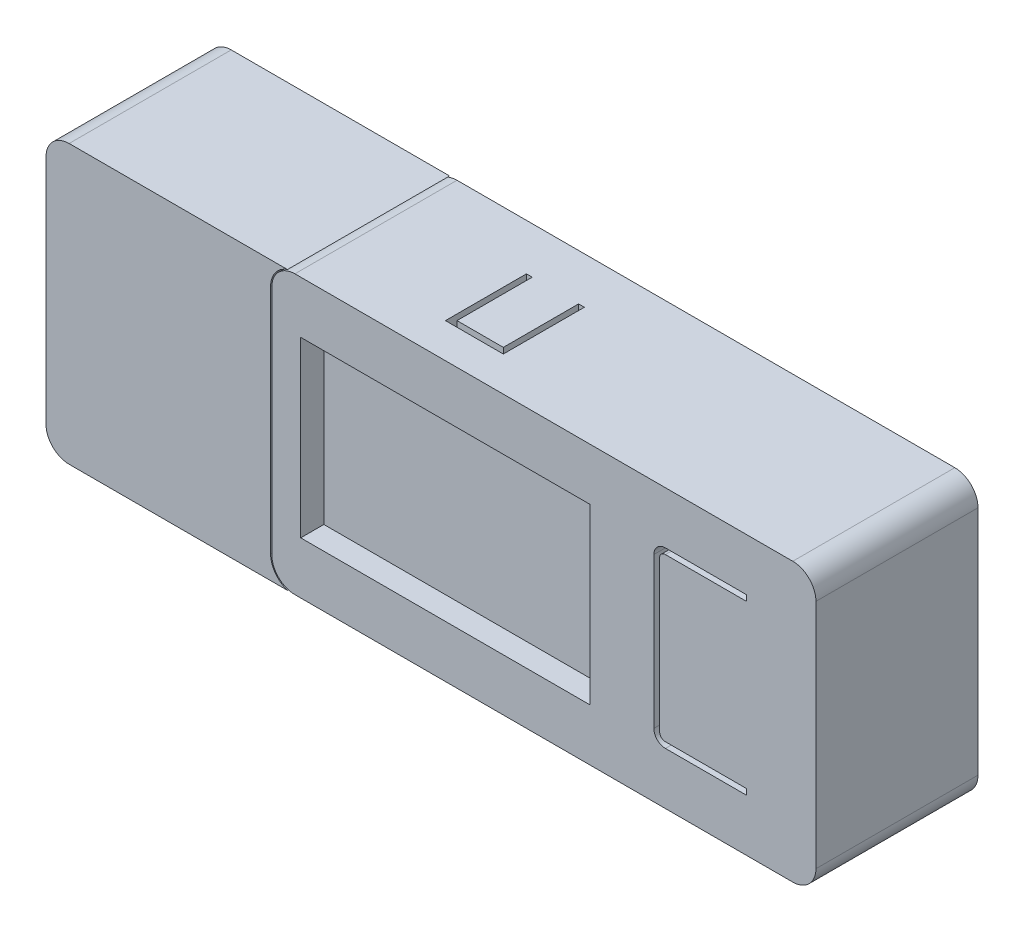
SolidWorks part; units mm, degrees
ref_plane "Alzado" through (0, 0, 0) normal (0, 0, 1) x (1, 0, 0)
ref_plane "Planta" through (0, 0, 0) normal (0, 1, 0) x (1, 0, 0)
ref_plane "Vista lateral" through (0, 0, 0) normal (1, 0, 0) x (0, 0, -1)
sketch "Croquis1" plane through (0, 0, 0) normal (0, 0, 1) x (1, 0, 0)
  line L1 (23.5, 12) -> (-23.5, 12)
  line L2 (23.5, 12) -> (23.5, -12)
  line L3 (23.5, -12) -> (-23.5, -12)
  line L4 (-23.5, 12) -> (-23.5, -12)
  line L5 (23.5, 12) -> (-23.5, -12) construction
  line L6 (23.5, -12) -> (-23.5, 12) construction
  point P0 (0, 0)
  dimension "D1" = 47
  dimension "D2" = 24
extrude "Saliente-Extruir1" add sketch "Croquis1" along normal blind 14
fillet "Redondeo1" radius 2 4 edges at (-23.5, -12, 7) (-23.5, 12, 7) (23.5, -12, 7) (23.5, 12, 7)
sketch "Croquis2" plane through (0, 0, 14) normal (0, 0, 1) x (1, 0, 0)
  line L0 (23.5, -10) -> (23.5, 10) construction
  line L1 (4, 7.5) -> (-21, 7.5)
  line L2 (4, 7.5) -> (4, -7.5)
  line L3 (4, -7.5) -> (-21, -7.5)
  line L4 (-21, 7.5) -> (-21, -7.5)
  line L5 (4, 7.5) -> (-21, -7.5) construction
  line L6 (4, -7.5) -> (-21, 7.5) construction
  line L7 (17.5, 7.5) -> (10.5, 7.5)
  line L8 (9.5, 6.5) -> (9.5, -6.5)
  line L9 (10.5, -7.5) -> (17.5, -7.5)
  line L10 (17.5, 7) -> (10.5, 7)
  line L11 (10, 6.5) -> (10, -6.5)
  line L12 (10.5, -7) -> (17.5, -7)
  line L13 (17.5, 7.5) -> (17.5, 7)
  line L14 (17.5, -7) -> (17.5, -7.5)
  arc A0 (10.5, 7.5) -> (9.5, 6.5) centre (10.5, 6.5) ccw
  arc A1 (9.5, -6.5) -> (10.5, -7.5) centre (10.5, -6.5) ccw
  arc A2 (10.5, 7) -> (10, 6.5) centre (10.5, 6.5) ccw
  arc A3 (10, -6.5) -> (10.5, -7) centre (10.5, -6.5) ccw
  point P0 (-8.5, 0)
  point P5 (9.5, 0)
  dimension "D6" = 1
  dimension "D1" = 25
  dimension "D2" = 19.5
  dimension "D3" = 15
  dimension "D4" = 8
  dimension "D5" = 6
  dimension "D7" = 0.5
extrude "Cortar-Extruir1" cut sketch "Croquis2" against normal blind 2
sketch "Croquis3" plane through (0, 12, 0) normal (0, 1, 0) x (1, 0, 0)
  line L0 (-6.5, -4) -> (-6.5, -11)
  line L1 (-6.5, -11) -> (-11.5, -11)
  line L2 (-11.5, -11) -> (-11.5, -4)
  line L3 (23.5, 0) -> (23.5, -14) construction
  line L4 (21.5, -14) -> (-21.5, -14) construction
  line L5 (21.5, 0) -> (-21.5, 0) construction
  line L6 (-7, -4) -> (-7, -10.5)
  line L7 (-7, -10.5) -> (-11, -10.5)
  line L8 (-11, -10.5) -> (-11, -4)
  line L9 (-11.5, -4) -> (-11, -4)
  line L10 (-7, -4) -> (-6.5, -4)
  dimension "D1" = 30
  dimension "D2" = 5
  dimension "D3" = 3
  dimension "D4" = 4
  dimension "D5" = 0.5
extrude "Cortar-Extruir2" cut sketch "Croquis3" against normal blind 5
sketch "Croquis4" plane through (0, -12, 0) normal (0, -1, 0) x (1, 0, 0)
  line L0 (16.5, 11) -> (16.5, 4)
  line L1 (16.5, 4) -> (11.5, 4)
  line L2 (11.5, 4) -> (11.5, 11)
  line L3 (23.5, 14) -> (23.5, 0) construction
  line L4 (-21.5, 14) -> (21.5, 14) construction
  line L5 (-21.5, 0) -> (21.5, 0) construction
  line L6 (16, 11) -> (16, 4.5)
  line L7 (16, 4.5) -> (12, 4.5)
  line L8 (12, 4.5) -> (12, 11)
  line L9 (11.5, 11) -> (12, 11)
  line L10 (16, 11) -> (16.5, 11)
  dimension "D1" = 5
  dimension "D2" = 7
  dimension "D3" = 3
  dimension "D4" = 4
  dimension "D5" = 0.5
extrude "Cortar-Extruir3" cut sketch "Croquis4" against normal blind 5
sketch "Croquis5" plane through (0, 0, 0) normal (0, 0, 1) x (1, 0, 0)
  line L0 (-22.1403, 12) -> (-41, 12)
  line L1 (-43, 10) -> (-43, -10)
  line L2 (-41, -12) -> (-22.1403, -12)
  line L3 (23.5, -10) -> (23.5, 10) construction
  line L9 (-23.6, 10) -> (-23.6, -10)
  line L10 (-23.6, 10) -> (-23.6, -10)
  arc A0 (-43, -10) -> (-41, -12) centre (-41, -10) ccw
  arc A1 (-41, 12) -> (-43, 10) centre (-41, 10) ccw
  arc A10 (-23.6, -10) -> (-21.5, -12.1) centre (-21.5, -10) ccw
  arc A11 (-21.5, 12.1) -> (-23.6, 10) centre (-21.5, 10) ccw
  arc A12 (-23.6, -10) -> (-22.1403, -12) centre (-21.5, -10) ccw
  arc A13 (-22.1403, 12) -> (-23.6, 10) centre (-21.5, 10) ccw
  point P5 (0, 0)
  dimension "D2" = 2
  dimension "D3" = 0.1
  dimension "D1" = 66.5
  dimension "D4" = 0.6403
  dimension "D5" = 0.6403
extrude "Saliente-Extruir3" add sketch "Croquis5" along normal up to surface (14 mm away) separate body up to face at (-8.5, 0, 14)
sketch "Croquis6" plane through (0, 0, 0) normal (0, 0, -1) x (-1, 0, 0)
  line L0 (-14, 8) -> (-14, -8) construction
  line L1 (43, 10) -> (43, -10) construction
  circle A0 centre (36, 0) radius 4.5
  circle A1 centre (-14, 8) radius 1
  circle A2 centre (-14, -8) radius 1
  point P6 (-14, 0)
  point P10 (0, 0)
  dimension "D1" = 2
  dimension "D4" = 9
  dimension "D5" = 7
  dimension "D2" = 57
  dimension "D3" = 16
extrude "Cortar-Extruir4" cut sketch "Croquis6" against normal blind 2
sketch "Croquis7" plane through (0, 0, 0) normal (0, 0, -1) x (-1, 0, 0)
  point P0 (36, 0)
  point P1 (36, 0)
